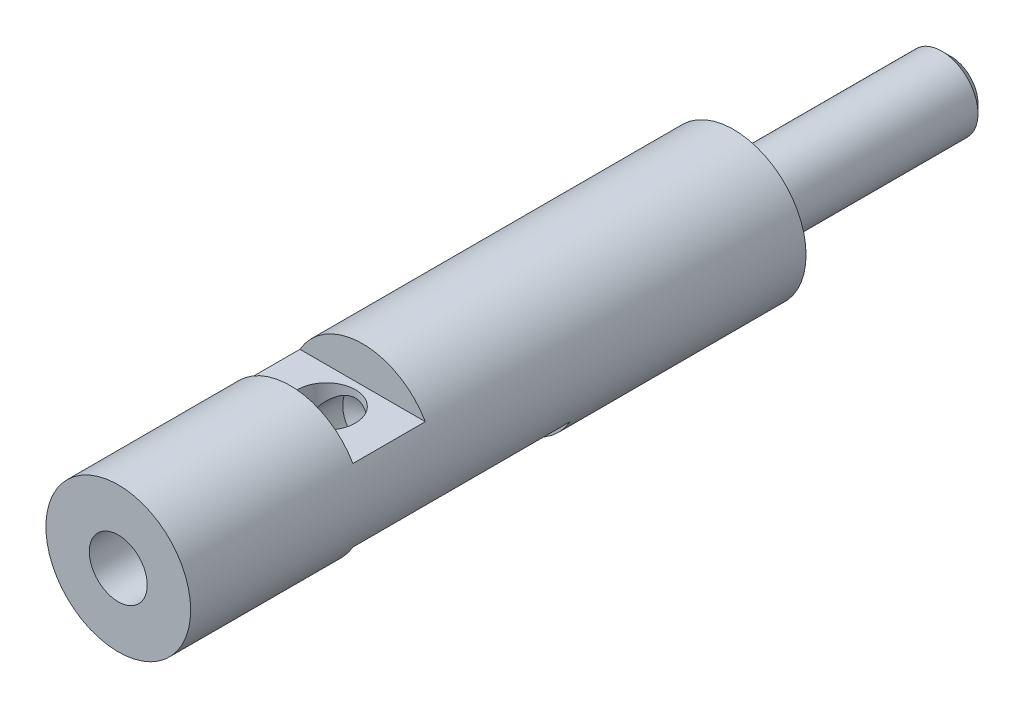
SolidWorks part; units mm, degrees
material "Brass"
ref_plane "Front Plane" through (0, 0, 0) normal (0, 0, 1) x (1, 0, 0)
ref_plane "Top Plane" through (0, 0, 0) normal (0, 1, 0) x (1, 0, 0)
ref_plane "Right Plane" through (0, 0, 0) normal (1, 0, 0) x (0, 0, -1)
sketch "Sketch1" plane through (0, 0, 0) normal (0, 0, 1) x (1, 0, 0)
  circle A0 centre (0, 0) radius 4
  dimension "D1" = 8
extrude "Boss-Extrude1" add sketch "Sketch1" along normal blind 34
sketch "Sketch2" plane through (0, 0, 0) normal (0, 0, -1) x (-1, 0, 0)
  circle A0 centre (0, 0) radius 2
  dimension "D1" = 4
extrude "Boss-Extrude2" add sketch "Sketch2" along normal blind 12
chamfer "Chamfer1" distance 0.5 angle 45 1 edges at (-2, 0, -12)
sketch "Sketch3" plane through (0, 0, 0) normal (1, 0, 0) x (0, 0, -1)
  line L0 (-24.5, -4) -> (-24.5, -2)
  line L1 (-34, -4) -> (0, -4) construction
  line L2 (-24.5, -2) -> (-12.5, -2)
  line L3 (-12.5, -2) -> (-12.5, -4)
  line L4 (-12.5, -4) -> (-24.5, -4)
  dimension "D1" = 9.5
  dimension "D2" = 12
  dimension "D3" = 2
extrude "Cut-Extrude1" cut sketch "Sketch3" against normal through all both and the other way through all
sketch "Sketch6" plane through (0, 0, 34) normal (0, 0, 1) x (1, 0, 0)
  point P0 (0, 0)
hole_wizard "Ø1.0mm Dowel Hole1" positions "Sketch6" profile "Sketch5" hole size "Ø1.0" standard "DIN"
sketch "Sketch5" plane through (0, 0, 34) normal (1, 0, 0) x (0, -1, 0)
  line L0 (0, 0) -> (0, 14.9614)
  line L1 (0, 14.9614) -> (1.6, 14)
  line L2 (1.6, 14) -> (1.6, 0)
  line L5 (1.6, 0) -> (0, 0)
  line L10 (0, 14.9614) -> (-1.6, 14) construction
  line L11 (0, -6.35) -> (0, 107.95) construction
  dimension "Hole Dia." = 3.2
  dimension "Hole Depth" = 14
  dimension "Drill Angle" = 118
sketch "Sketch7" plane through (0, 0, 0) normal (1, 0, 0) x (0, 0, -1)
  line L0 (-24.5, 4) -> (-24.5, 2)
  line L1 (0, 4) -> (-34, 4) construction
  line L2 (-24.5, 2) -> (-20.5, 2)
  line L3 (-20.5, 2) -> (-20.5, 4)
  line L4 (-20.5, 4) -> (-24.5, 4)
  point P6 (-22.5, 4)
  dimension "D1" = 4
  dimension "D2" = 2
  dimension "D3" = 11.5
extrude "Cut-Extrude2" cut sketch "Sketch7" against normal through all both and the other way through all
sketch "Sketch10" plane through (0, 2, 0) normal (0, 1, 0) x (1, 0, 0)
  line L0 (-3.4641, -24.5) -> (3.4641, -24.5) construction
  point P0 (0, -22.5)
  dimension "D1" = 2
hole_wizard "Ø1.5mm Dowel Hole1" positions "Sketch10" profile "Sketch11" hole size "Ø1.5" standard "DIN"
sketch "Sketch11" plane through (0, 2, 22.5) normal (1, 0, 0) x (0, 0, 1)
  line L0 (0, 0) -> (0, 2.9604)
  line L1 (0, 2.9604) -> (1.6, 1.999)
  line L2 (1.6, 1.999) -> (1.6, 0)
  line L5 (1.6, 0) -> (0, 0)
  line L10 (0, 2.9604) -> (-1.6, 1.999) construction
  line L11 (0, -6.35) -> (0, 107.95) construction
  dimension "Hole Dia." = 3.2
  dimension "Hole Depth" = 1.999
  dimension "Drill Angle" = 118
